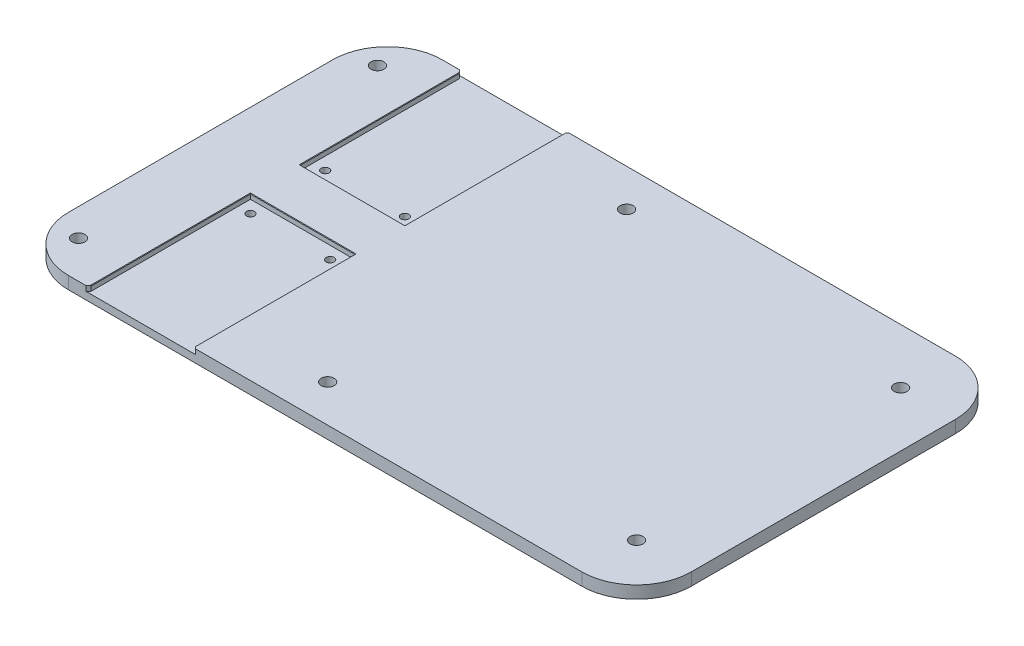
SolidWorks part; units mm, degrees
ref_plane "前视基准面" through (0, 0, 0) normal (0, 0, 1) x (1, 0, 0)
ref_plane "上视基准面" through (0, 0, 0) normal (0, 1, 0) x (1, 0, 0)
ref_plane "右视基准面" through (0, 0, 0) normal (1, 0, 0) x (0, 0, -1)
other "Configuration Table"
sketch "草图1" plane through (0, 0, 0) normal (0, 1, 0) x (1, 0, 0)
  line L0 (103, 75) -> (-103, 75)
  line L5 (-125, 53) -> (-125, -53)
  line L6 (-103, -75) -> (103, -75)
  line L7 (125, -53) -> (125, 53)
  arc A0 (125, 53) -> (103, 75) centre (103, 53) ccw
  arc A1 (-103, 75) -> (-125, 53) centre (-103, 53) ccw
  arc A2 (-125, -53) -> (-103, -75) centre (-103, -53) ccw
  arc A3 (103, -75) -> (125, -53) centre (103, -53) ccw
  circle A4 centre (-114, 60) radius 2.6
  circle A5 centre (-14, 60) radius 2.6
  circle A6 centre (103, 53) radius 2.6
  circle A7 centre (-114, -60) radius 2.6
  circle A8 centre (-14, -60) radius 2.6
  circle A9 centre (103, -53) radius 2.6
  point P26 (0, 0)
  dimension "D3" = 22
  dimension "D4" = 22
  dimension "D5" = 22
  dimension "D6" = 22
  dimension "D9" = 100
  dimension "D10" = 117
  dimension "D11" = 106
  dimension "D12" = 117
  dimension "D13" = 100
  dimension "D14" = 120
  dimension "D15" = 7
  dimension "D16" = 11
  dimension "D1" = 150
  dimension "D2" = 250
  dimension "D7" = 125
  dimension "D8" = 75
extrude "凸台-拉伸1" add sketch "草图1" along normal blind 5
sketch "草图2" plane through (0, 5, 0) normal (0, 1, 0) x (1, 0, 0)
  line L0 (-103, -75) -> (103, -75) construction
  line L1 (-95, -75) -> (-53, -75)
  line L2 (-95, -75) -> (-95, -10)
  line L3 (-95, -10) -> (-53, -10)
  line L4 (-53, -75) -> (-53, -10)
  line L5 (-125, 53) -> (-125, -53) construction
  line L6 (-1000, 0) -> (49000, 0) construction
  line L7 (-53, 75) -> (-53, 10)
  line L8 (-95, 10) -> (-53, 10)
  line L9 (-95, 75) -> (-95, 10)
  line L10 (-95, 75) -> (-53, 75)
  dimension "D1" = 42
  dimension "D2" = 30
  dimension "D3" = 65
extrude "切除-拉伸1" cut sketch "草图2" against normal blind 2
chamfer "倒角1" distance 0.2 angle 45 6 edges at (-53, 5, -42.5) (-74, 5, -10) (-95, 5, -42.5) (-53, 5, 42.5) (-74, 5, 10) (-95, 5, 42.5)
chamfer "倒角2" distance 1 angle 45 4 edges at (-53, 3.9, 75) (-95, 3.9, 75) (-95, 3.9, -75) (-53, 3.9, -75)
sketch "草图3" plane through (0, 3, 0) normal (0, 1, 0) x (1, 0, 0)
  line L0 (-1000, 0) -> (49000, 0) construction
  line L1 (-95, 10) -> (-53, 10) construction
  line L2 (-53, 10) -> (-53, 74) construction
  line L3 (-95, 74) -> (-95, 10) construction
  circle A0 centre (-90, 15) radius 1.6
  circle A1 centre (-58, 15) radius 1.6
  circle A2 centre (-58, -15) radius 1.6
  circle A3 centre (-90, -15) radius 1.6
  dimension "D1" = 3.2
  dimension "D2" = 3.2
  dimension "D3" = 5
  dimension "D4" = 5
  dimension "D5" = 5
  dimension "D6" = 5
extrude "切除-拉伸2" cut sketch "草图3" against normal blind 3
